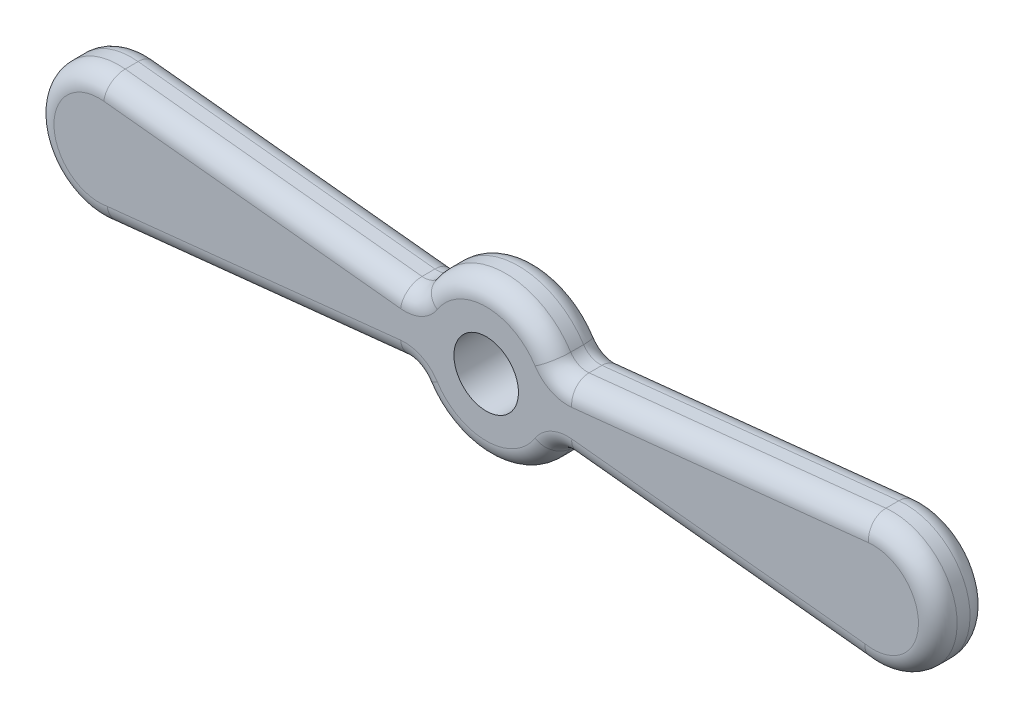
SolidWorks part; units mm, degrees
material "Mahogany"
ref_plane "Front" through (0, 0, 0) normal (0, 0, 1) x (1, 0, 0)
ref_plane "Top" through (0, 0, 0) normal (0, 1, 0) x (1, 0, 0)
ref_plane "Right" through (0, 0, 0) normal (1, 0, 0) x (0, 0, -1)
sketch "Sketch1" plane through (0, 0, 0) normal (0, 0, 1) x (1, 0, 0)
  line L0 (-58.9547, 9.9452) -> (-12.9432, 5.1092)
  line L2 (58.9547, 9.9452) -> (12.9432, 5.1092)
  line L3 (-60, 0) -> (60, 0) construction
  line L5 (-12.955, -5.0907) -> (-58.3333, -9.8601)
  line L6 (12.955, -5.0907) -> (58.3333, -9.8601)
  arc A0 (-10.1132, -6.4594) -> (10.1132, -6.4594) centre (0, 0) ccw
  arc A1 (58.3333, -9.8601) -> (58.9547, 9.9452) centre (60, 0) ccw
  arc A2 (-58.9547, 9.9452) -> (-58.3333, -9.8601) centre (-60, 0) ccw
  circle A3 centre (0, 0) radius 5
  arc A4 (10.1037, 6.4742) -> (-10.1037, 6.4742) centre (0, 0) ccw
  arc A5 (12.9432, 5.1092) -> (10.1037, 6.4742) centre (12.6296, 8.0928) cw
  arc A6 (12.955, -5.0907) -> (10.1132, -6.4594) centre (12.6415, -8.0742) ccw
  arc A7 (-12.955, -5.0907) -> (-10.1132, -6.4594) centre (-12.6415, -8.0742) cw
  arc A8 (-12.9432, 5.1092) -> (-10.1037, 6.4742) centre (-12.6296, 8.0928) ccw
  point P11 (10.9539, 4.9001)
  dimension "D3" = 10
  dimension "D4" = 60
  dimension "D5" = 10
  dimension "D1" = 3
  dimension "D2" = 120
  dimension "D6" = 12
  dimension "D7" = 12
  dimension "D8" = 6
  dimension "D9" = 6
  dimension "D10" = 12
extrude "Boss-Extrude1" add sketch "Sketch1" along normal mid plane 8
fillet "Fillet2" radius 3 24 edges at (-35.6442, -7.4754, -4) (-11.3397, -5.3714, -4) (0, -12, -4) (11.3397, -5.3714, -4) (-69.9951, -0.3136, -4) (-35.949, 7.5272, -4) (-11.3298, 5.389, -4) (0, 12, -4) (11.3298, 5.389, -4) (-35.6442, -7.4754, 4) (-11.3397, -5.3714, 4) (0, -12, 4) (11.3397, -5.3714, 4) (-69.9951, -0.3136, 4) (35.6442, -7.4754, -4) (35.949, 7.5272, -4) (69.9951, -0.3136, -4) (35.6442, -7.4754, 4) (69.9951, -0.3136, 4) (35.949, 7.5272, 4) (-11.3298, 5.389, 4) (11.3298, 5.389, 4) (0, 12, 4) (-35.949, 7.5272, 4)
